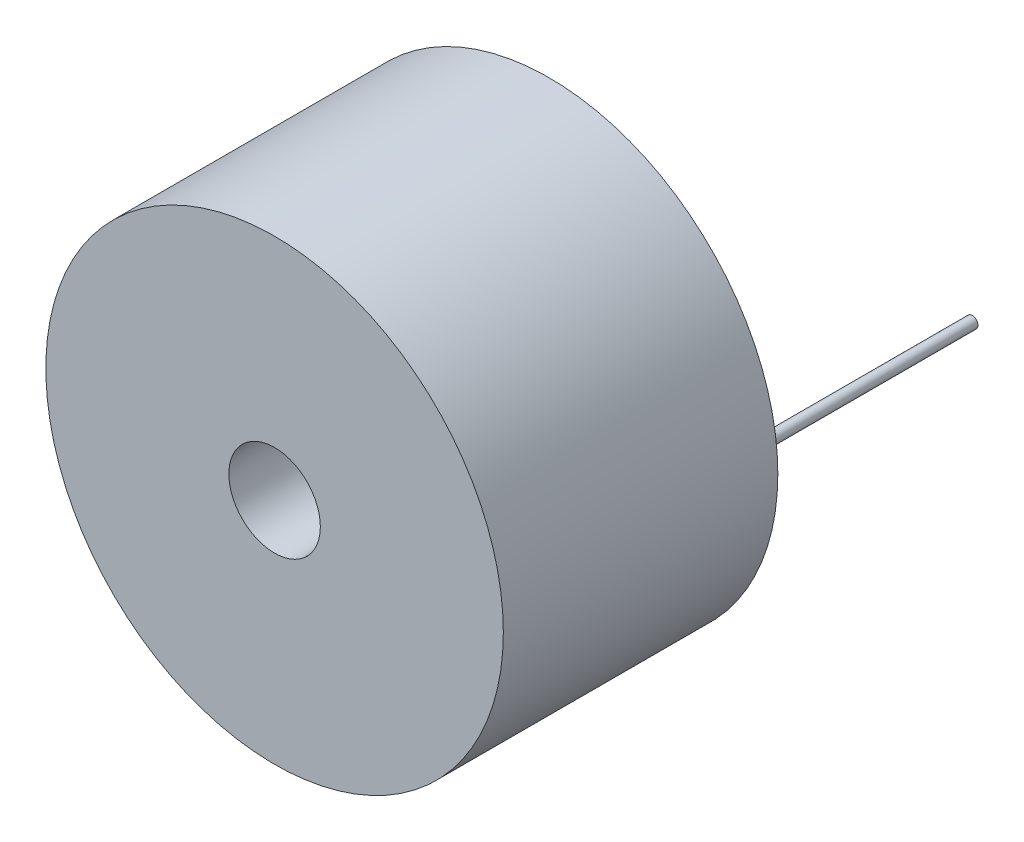
SolidWorks part; units mm, degrees
ref_plane "Front Plane" through (0, 0, 0) normal (0, 0, 1) x (1, 0, 0)
ref_plane "Top Plane" through (0, 0, 0) normal (0, 1, 0) x (1, 0, 0)
ref_plane "Right Plane" through (0, 0, 0) normal (1, 0, 0) x (0, 0, -1)
sketch "Sketch1" plane through (0, 0, 0) normal (0, 0, 1) x (1, 0, 0)
  circle A0 centre (0, 0) radius 10
  dimension "D1" = 20
extrude "Boss-Extrude1" add sketch "Sketch1" along normal blind 12
sketch "Sketch2" plane through (0, 0, 12) normal (0, 0, 1) x (1, 0, 0)
  circle A0 centre (0, 0) radius 2
  dimension "D1" = 4
extrude "Cut-Extrude1" cut sketch "Sketch2" against normal blind 10
sketch "Sketch3" plane through (0, 0, 0) normal (0, 0, -1) x (-1, 0, 0)
  circle A0 centre (-8.5, 0) radius 0.25
  circle A1 centre (8.5, 0) radius 0.25
  dimension "D1" = 0.5
  dimension "D2" = 0.5
  dimension "D3" = 8.5
  dimension "D4" = 8.5
extrude "Boss-Extrude2" add sketch "Sketch3" along normal blind 10 contours A0 region at (8.5, 0, 0)
extrude "Boss-Extrude3" add sketch "Sketch3<3>" along normal blind 8 contours A1 region at (-8.5, 0, 0)
sketch "Sketch3<3>" plane through (0, 0, 0) normal (0, 0, -1) x (-1, 0, 0) same geometry as "Sketch3"
